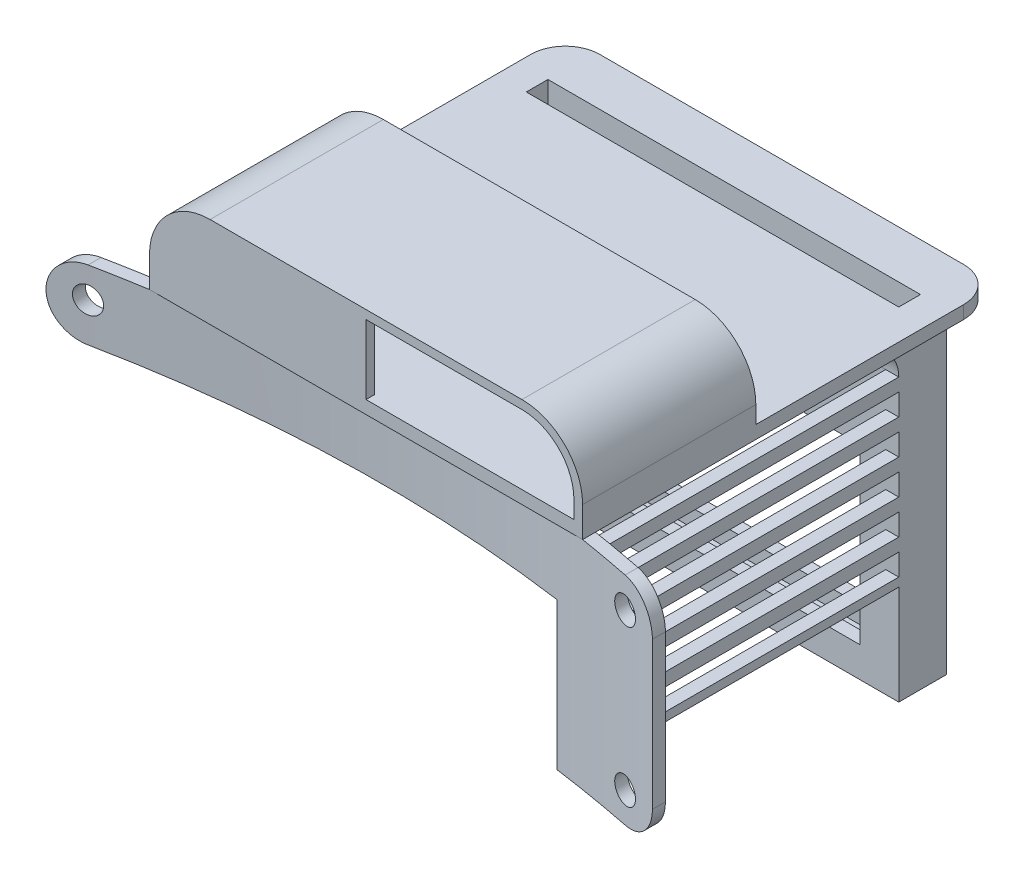
SolidWorks part; units mm, degrees
ref_plane "前视基准面" through (0, 0, 0) normal (0, 0, 1) x (1, 0, 0)
ref_plane "上视基准面" through (0, 0, 0) normal (0, 1, 0) x (1, 0, 0)
ref_plane "右视基准面" through (0, 0, 0) normal (1, 0, 0) x (0, 0, -1)
sketch "草图1" plane through (0, 0, 0) normal (0, 1, 0) x (1, 0, 0)
  line L0 (25, 0) -> (25, 48) construction
  line L1 (0, 0) -> (50, 0)
  line L2 (0, 0) -> (0, 48)
  line L3 (0, 48) -> (50, 48)
  line L4 (50, 0) -> (50, 48)
  line L5 (3.5, 42.5) -> (46.5, 42.5)
  line L6 (3.5, 42.5) -> (3.5, 40)
  line L7 (3.5, 40) -> (46.5, 40)
  line L8 (46.5, 42.5) -> (46.5, 40)
  point P11 (25, 42.5)
  dimension "D1" = 50
  dimension "D2" = 43
  dimension "D3" = 2.5
  dimension "D4" = 40
  dimension "D5" = 48
extrude "凸台-拉伸1" add sketch "草图1" along normal blind 1.5
sketch "草图2" plane through (0, 0, 0) normal (0, -1, 0) x (1, 0, 0)
  line L0 (2, -44) -> (2, -38.5)
  line L1 (3.5, -42.5) -> (46.5, -42.5)
  line L2 (3.5, -42.5) -> (3.5, -40)
  line L3 (3.5, -40) -> (46.5, -40)
  line L4 (46.5, -42.5) -> (46.5, -40)
  line L5 (2, -38.5) -> (48, -38.5)
  line L6 (48, -44) -> (48, -38.5)
  line L7 (2, -44) -> (48, -44)
  dimension "D1" = 1.5
extrude "凸台-拉伸2" add sketch "草图2" along normal blind 35
sketch "草图3" plane through (0, -35, 0) normal (0, -1, 0) x (1, 0, 0)
  line L1 (48, -38.5) -> (2, -38.5)
  line L2 (48, -38.5) -> (48, -44)
  line L3 (48, -44) -> (2, -44)
  line L4 (2, -38.5) -> (2, -44)
extrude "凸台-拉伸3" add sketch "草图3" along normal blind 1.5
sketch "草图4" plane through (0, 0, -44) normal (0, 0, -1) x (-1, 0, 0)
  line L0 (-25, -36.5) -> (-25, 8.4577) construction
  line L1 (-2, -36.5) -> (-48, -36.5) construction
  line L2 (-6.5, -33) -> (-43.5, -33)
  line L3 (-43.5, -33) -> (-43.5, -13)
  line L4 (-43.5, -13) -> (-6.5, -13)
  line L5 (-6.5, -33) -> (-6.5, -13)
  point P9 (-25, -13)
  point P10 (-25, -33)
  dimension "D1" = 3.5
  dimension "D2" = 37
  dimension "D3" = 20
extrude "切除-拉伸1" cut sketch "草图4" against normal blind 5.5
sketch "草图5" plane through (0, 0, 0) normal (0, -1, 0) x (1, 0, 0)
  line L0 (25, 0) -> (25, 57.502) construction
  line L1 (0, 0) -> (50, 0) construction
  line L6 (25, -2) -> (-4.7424, -2) construction
  line L7 (-10, 0.4445) -> (-10, 1.9445)
  line L8 (60, 0.4445) -> (60, 1.9445)
  arc A0 (-10, 1.9445) -> (60, 1.9445) centre (25, 155.25) ccw
  arc A1 (-10, 0.4445) -> (60, 0.4445) centre (25, 155.25) ccw
  dimension "D1" = 2
  dimension "D2" = 1.5
  dimension "D3" = 35
extrude "凸台-拉伸4" add sketch "草图5" along normal blind 25
sketch "草图6" plane through (48, 0, 0) normal (1, 0, 0) x (0, 0, -1)
  line L1 (44, 0) -> (1, 0)
  line L2 (44, 0) -> (44, -25)
  line L3 (44, -25) -> (1, -25)
  line L4 (1, 0) -> (1, -25)
  line L11 (0, 1.5) -> (0, 0) construction
  line L12 (38.5, -36.5) -> (38.5, 0) construction
  line L13 (3.5, -1.5) -> (38.5, -1.5)
  line L14 (3.5, -1.5) -> (3.5, -4)
  line L15 (3.5, -4) -> (38.5, -4)
  line L16 (38.5, -1.5) -> (38.5, -4)
  line L35 (3.5, -5.5) -> (38.5, -5.5)
  line L36 (3.5, -5.5) -> (3.5, -8)
  line L37 (3.5, -8) -> (38.5, -8)
  line L38 (38.5, -5.5) -> (38.5, -8)
  line L39 (3.5, -9.5) -> (38.5, -9.5)
  line L40 (3.5, -9.5) -> (3.5, -12)
  line L41 (3.5, -12) -> (38.5, -12)
  line L42 (38.5, -9.5) -> (38.5, -12)
  line L43 (3.5, -13.5) -> (38.5, -13.5)
  line L44 (3.5, -13.5) -> (3.5, -16)
  line L45 (3.5, -16) -> (38.5, -16)
  line L46 (38.5, -13.5) -> (38.5, -16)
  line L47 (3.5, -17.5) -> (38.5, -17.5)
  line L48 (3.5, -17.5) -> (3.5, -20)
  line L49 (3.5, -20) -> (38.5, -20)
  line L50 (38.5, -17.5) -> (38.5, -20)
  line L51 (3.5, -21.5) -> (38.5, -21.5)
  line L52 (3.5, -21.5) -> (3.5, -24)
  line L53 (3.5, -24) -> (38.5, -24)
  line L54 (38.5, -21.5) -> (38.5, -24)
  dimension "D1" = 1.5
  dimension "D2" = 2.5
  dimension "D3" = 35
  dimension "D4" = 1
  dimension "D5" = 6
extrude "凸台-拉伸5" add sketch "草图6" against normal blind 1.5
sketch "草图7" plane through (0, 0, 0) normal (0, 0, 1) x (1, 0, 0)
  line L1 (-10, -8) -> (46.5, -8)
  line L2 (-10, -8) -> (-10, -25)
  line L3 (-10, -25) -> (46.5, -25)
  line L4 (46.5, -8) -> (46.5, -25)
  line L5 (-10, -25) -> (60, -25) construction
  line L6 (0, 0) -> (50, 0) construction
  line L8 (-10, -25) -> (-10, 0) construction
  line L9 (48, -36.5) -> (48, -25) construction
  line L10 (25, 0) -> (25, -45.3003) construction
  line L11 (0, 0) -> (50, 0) construction
  line L12 (0, 0) -> (-10, 0) construction
  line L13 (60, -12.5) -> (-15.1348, -12.5) construction
  line L14 (60, -25) -> (60, 0) construction
  circle A0 centre (-6, -3.5) radius 1.5
  circle A1 centre (56, -3.5) radius 1.5
  circle A2 centre (56, -21.5) radius 1.5
  dimension "D3" = 3
  dimension "D1" = 8
  dimension "D2" = 1.5
  dimension "D4" = 3.5
  dimension "D5" = 31
extrude "切除-拉伸2" cut sketch "草图7" against normal up to next and the other way blind 10
sketch "草图8" plane through (0, 1.5, 0) normal (0, 1, 0) x (1, 0, 0)
  line L0 (25, 0) -> (25, 29.9328) construction
  line L1 (50, 0) -> (49, 0)
  line L2 (50, 0) -> (50, 20)
  line L3 (50, 20) -> (49, 20)
  line L4 (49, 0) -> (49, 20)
  line L5 (0, 0) -> (50, 0) construction
  line L6 (1, 1) -> (1, 20)
  line L7 (0, 20) -> (1, 20)
  line L8 (0, 0) -> (0, 20)
  line L10 (25, 0) -> (25, 1)
  line L11 (25, 1) -> (1, 1)
  line L12 (0, 0) -> (25, 0)
  dimension "D1" = 48
  dimension "D2" = 20
  dimension "D3" = 1
extrude "凸台-拉伸6" add sketch "草图8" along normal blind 8
sketch "草图9" plane through (0, 9.5, 0) normal (0, 1, 0) x (1, 0, 0)
  line L1 (50, 20) -> (0, 20)
  line L2 (50, 20) -> (50, 0)
  line L3 (50, 0) -> (0, 0)
  line L4 (0, 20) -> (0, 0)
extrude "凸台-拉伸7" add sketch "草图9" along normal blind 1
fillet "圆角1" radius 4 8 edges at (50, 0.75, -48) (0, 0.75, -48) (-10, 0, 1.1945) (-10, -8, 1.1945) (60, 0, 1.1945) (60, -25, 1.1945) (24.25, 0, -38.5) (23.2309, 0, -3.4529)
fillet "圆角2" radius 6 2 edges at (1, 9.5, -10.5) (49, 9.5, -10)
fillet "圆角3" radius 7 2 edges at (0, 10.5, -10) (50, 10.5, -10)
